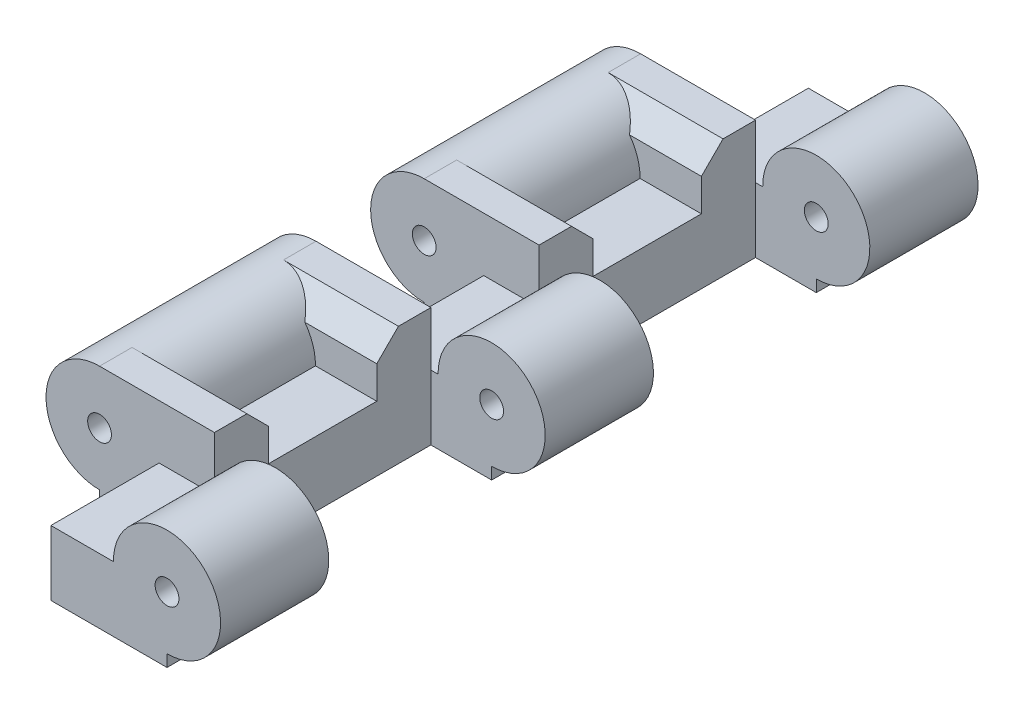
SolidWorks part; units mm, degrees
ref_plane "Front Plane" through (0, 0, 0) normal (0, 0, 1) x (1, 0, 0)
ref_plane "Top Plane" through (0, 0, 0) normal (0, 1, 0) x (1, 0, 0)
ref_plane "Right Plane" through (0, 0, 0) normal (1, 0, 0) x (0, 0, -1)
sketch "Sketch1" plane through (0, 0, 0) normal (0, 1, 0) x (1, 0, 0)
  line L0 (0, 0) -> (10.6165, 0) construction
  line L1 (10.6165, 10) -> (0, 10)
  line L2 (10.6165, 10) -> (10.6165, -10)
  line L3 (10.6165, -10) -> (0, -10)
  line L4 (0, 10) -> (0, -10)
  line L5 (5.5005, -10) -> (16.2325, -10)
  line L6 (5.5005, -10) -> (5.5005, -20)
  line L7 (5.5005, -20) -> (16.2325, -20)
  line L8 (16.2325, -10) -> (16.2325, -20)
  line L13 (5.5005, 20) -> (16.2325, 20)
  line L14 (16.2325, 10) -> (16.2325, 20)
  line L15 (5.5005, 10) -> (16.2325, 10)
  line L16 (5.5005, 10) -> (5.5005, 20)
  line L17 (5.5005, 15) -> (16.2325, 15) construction
  line L18 (16.2325, 20) -> (16.2325, 10)
  line L19 (5.5005, 20) -> (16.2325, 20)
  line L20 (5.5005, 20) -> (5.5005, 10)
  line L21 (10.6165, 40) -> (0, 40)
  line L22 (0, 20) -> (0, 40)
  line L23 (10.6165, 20) -> (0, 20)
  line L24 (10.6165, 20) -> (10.6165, 40)
  line L25 (5.5005, 50) -> (16.2325, 50)
  line L26 (16.2325, 40) -> (16.2325, 50)
  line L27 (5.5005, 40) -> (16.2325, 40)
  line L28 (5.5005, 40) -> (5.5005, 50)
  point P4 (0, 0)
  dimension "D1" = 10.732
  dimension "D2" = 10.6165
  dimension "D3" = 5.116
  dimension "D4" = 10
  dimension "D5" = 20
  dimension "D6" = 70
extrude "Boss-Extrude1" add sketch "Sketch1" along normal blind 6 contours L8 L5 L3 L6 L7 | L0 L4 L3 L2 | L4 L0 L2 L1 | L16 L1 L15 L14 L13 | L21 L22 L23 L24 | L25 L26 L27 L28 region at (5.3083, 0, 0) region at (10.8665, 0, -15) region at (10.8665, 0, 15)
sketch "Sketch2" plane through (0, 6, 0) normal (0, 1, 0) x (1, 0, 0)
  line L0 (10.6165, 10) -> (10.6165, -10) construction
  line L1 (0, 10) -> (0, -10) construction
  line L2 (10.6165, 10) -> (10.6165, 5)
  line L3 (0, 10) -> (0, 5)
  line L4 (10.6165, -10) -> (0, -10)
  line L5 (10.6165, 10) -> (0, 10)
  line L6 (10.6165, -5) -> (0, -5)
  line L7 (0, 0) -> (10.6165, 0) construction
  line L8 (10.6165, 5) -> (0, 5)
  line L9 (0, -5) -> (0, -10)
  line L10 (10.6165, -5) -> (10.6165, -10)
  line L11 (5.5005, 15) -> (16.2325, 15) construction
  line L12 (5.5005, 10) -> (5.5005, 20) construction
  line L13 (16.2325, 10) -> (16.2325, 20) construction
  line L14 (10.6165, 35) -> (10.6165, 40)
  line L15 (10.6165, 35) -> (0, 35)
  line L16 (0, 35) -> (0, 40)
  line L17 (10.6165, 40) -> (0, 40)
  line L18 (10.6165, 20) -> (0, 20)
  line L19 (0, 20) -> (0, 25)
  line L20 (10.6165, 25) -> (0, 25)
  line L21 (10.6165, 20) -> (10.6165, 25)
  dimension "D1" = 5
extrude "Boss-Extrude2" add sketch "Sketch2" along normal blind 5
chamfer "Chamfer1" distance 2 4 edges at (5.3083, 11, -5) (5.3083, 11, 5) (5.3082, 11, -35) (5.3082, 11, -25)
ref_plane "Plane1" through (0, 0, 0) normal (0, 0, 1) x (1, 0, 0)
sketch "Sketch3" plane through (0, 0, 0) normal (0, 0, 1) x (1, 0, 0)
  line L0 (0, 11) -> (0, 0) construction
  line L1 (5.5005, 0) -> (0, 0) construction
  line L2 (5.5005, 0) -> (0, 0) construction
  line L3 (0, 11) -> (10.6165, 11) construction
  line L4 (0, 11) -> (10.6165, 11) construction
  line L5 (16.2325, 6) -> (16.2325, 0) construction
  line L6 (16.2325, 6) -> (16.2325, 0)
  circle A0 centre (0, 6.05) radius 4.95
  circle A1 centre (16.2325, 6.05) radius 4.95
  point P4 (0, 1.1)
  point P7 (0, 11)
  point P14 (0, 0)
  point P15 (16.2325, 1.1)
  point P16 (0, 0)
  dimension "D1" = 1.1
extrude "Boss-Extrude3" add sketch "Sketch3" along normal up to surface (10 mm away) from surface contours A0 region at (0, 6.05, 0) up to face at (5.3723, 5.6667, 10) starting at face at (5.3723, 5.6667, -10)
extrude "Boss-Extrude4" add sketch "Sketch3<3>" along normal up to surface (20 mm away) from surface contours A1 region at (16.2325, 6.05, 0) up to face at (10.8665, 3, 20) starting at face at (13.4245, 3, 10)
sketch "Sketch3<3>" plane through (0, 0, 0) normal (0, 0, 1) x (1, 0, 0) same geometry as "Sketch3"
extrude "Boss-Extrude5" add sketch "Sketch3<4>" along normal up to surface (-10 mm away) from surface contours A1 region at (16.2325, 6.05, 0) up to face at (13.4245, 3, -10) starting at face at (13.4245, 3, -20)
sketch "Sketch3<4>" plane through (0, 0, 0) normal (0, 0, 1) x (1, 0, 0) same geometry as "Sketch3"
extrude "Boss-Extrude6" add sketch "Sketch3<5>" along normal up to surface (-20 mm away) from surface contours A0 region at (0, 6.05, 0) up to face at (5.3723, 5.6667, -20) starting at face at (5.3723, 5.6667, -40)
sketch "Sketch3<5>" plane through (0, 0, 0) normal (0, 0, 1) x (1, 0, 0) same geometry as "Sketch3"
extrude "Boss-Extrude7" add sketch "Sketch3<6>" along normal up to surface (-40 mm away) from surface contours A1 region at (16.2325, 6.05, 0) up to face at (13.4245, 3, -40) starting at face at (10.8665, 3, -50)
sketch "Sketch3<6>" plane through (0, 0, 0) normal (0, 0, 1) x (1, 0, 0) same geometry as "Sketch3"
sketch "Sketch6" plane through (0, 0, 20) normal (0, 0, 1) x (1, 0, 0)
  arc A0 (0, 11) -> (0, 1.1) centre (0, 6.05) ccw construction
  arc A1 (16.2325, 1.1) -> (11.2828, 6) centre (16.2325, 6.05) ccw construction
  arc A2 (0, 11) -> (0, 1.1) centre (0, 6.05) ccw construction
  arc A3 (16.2325, 1.1) -> (11.2828, 6) centre (16.2325, 6.05) ccw construction
sketch "Sketch7" plane through (0, 0, 20) normal (0, 0, 1) x (1, 0, 0)
  point P0 (0, 6.05)
  point P3 (16.2325, 6.05)
hole_wizard "Ø1.0mm Dowel Hole1" positions "Sketch7" profile "Sketch8" hole size "Ø1.0" standard "ANSI Metric" end condition through all
sketch "Sketch8" plane through (0, 6.05, 20) normal (1, 0, 0) x (0, -1, 0)
  line L0 (0, 0) -> (0, 70)
  line L1 (0, 70) -> (1.1, 70)
  line L2 (1.1, 70) -> (1.1, 0)
  line L5 (1.1, 0) -> (0, 0)
  line L11 (0, -6.35) -> (0, 107.95) construction
  dimension "Thru Hole Dia." = 2.2
  dimension "Thru Hole Depth" = 70
